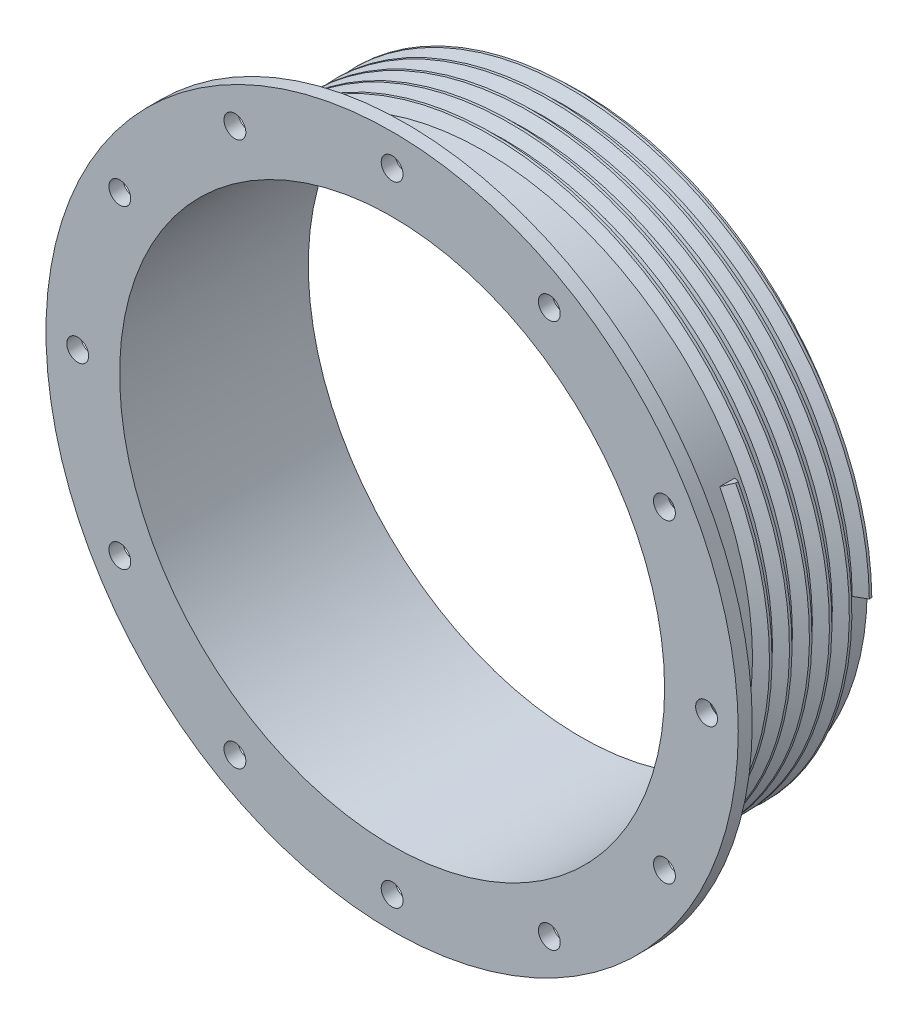
SolidWorks part; units mm, degrees
material "6061-T6 (SS)"
ref_plane "Front Plane" through (0, 0, 0) normal (0, 0, 1) x (1, 0, 0)
ref_plane "Top Plane" through (0, 0, 0) normal (0, 1, 0) x (1, 0, 0)
ref_plane "Right Plane" through (0, 0, 0) normal (1, 0, 0) x (0, 0, -1)
sketch "Sketch1" plane through (0, 0, 0) normal (0, 1, 0) x (1, 0, 0)
  line L0 (0, 0) -> (0, 40.64) construction
  line L1 (49.53, 0) -> (62.9158, 0)
  line L2 (62.9158, 0) -> (62.9158, 2.54)
  line L3 (62.9158, 2.54) -> (52.07, 2.54)
  line L4 (52.07, 2.54) -> (52.07, 34.29)
  line L5 (52.07, 34.29) -> (49.53, 34.29)
  line L6 (49.53, 34.29) -> (49.53, 0)
  dimension "D1" = 2.54
  dimension "D2" = 2.54
  dimension "D3" = 62.9158
  dimension "D4" = 49.53
  dimension "D5" = 34.29
revolve "Revolve1" add sketch "Sketch1" angle 360 about L0
sketch "Sketch2" plane through (0, 0, -2.54) normal (0, 0, -1) x (-1, 0, 0)
  circle A0 centre (0, 57.15) radius 1.9844
  dimension "D2" = 3.9688
  dimension "D1" = 57.15
extrude "Cut-Extrude1" cut sketch "Sketch2" against normal up to surface (2.54 mm away) up to face at (62.9158, 0, 0)
pattern_circular "CirPattern1" count 12 over 360 about axis through (0, 0, -34.29) along (0, 0, 1) of "Cut-Extrude1"
thread "Thread2" pitch 3.6286 method extrude profile "Thread Profile2" start angle 0, offset 0, length 18.415, pitch 3.6286, diameter 104.14
ref_plane "Plane2" through (52.07, 0, -34.29) normal (0, -1, 0) x (1, 0, 0)
sketch "Thread Profile2" plane through (52.07, 0, -34.29) normal (0, -1, 0) x (1, 0, 0)
  line L0 (0, 0) -> (0, 3.6286) construction
  line L1 (0, 0) -> (1.964, 1.1339)
  line L2 (1.964, 1.1339) -> (1.964, 1.5875)
  line L3 (1.964, 1.5875) -> (0, 2.7214)
  line L4 (1.964, 1.3607) -> (0, 1.3607) construction
  line L11 (0, 0) -> (0, 2.7214)
  point P2 (0, 0)
  dimension "Pitch" = 3.6286
  dimension "Profile_Angle" = 60
  dimension "Profile_Land" = 0.4536
  dimension "Profile_Height" = 1.964
